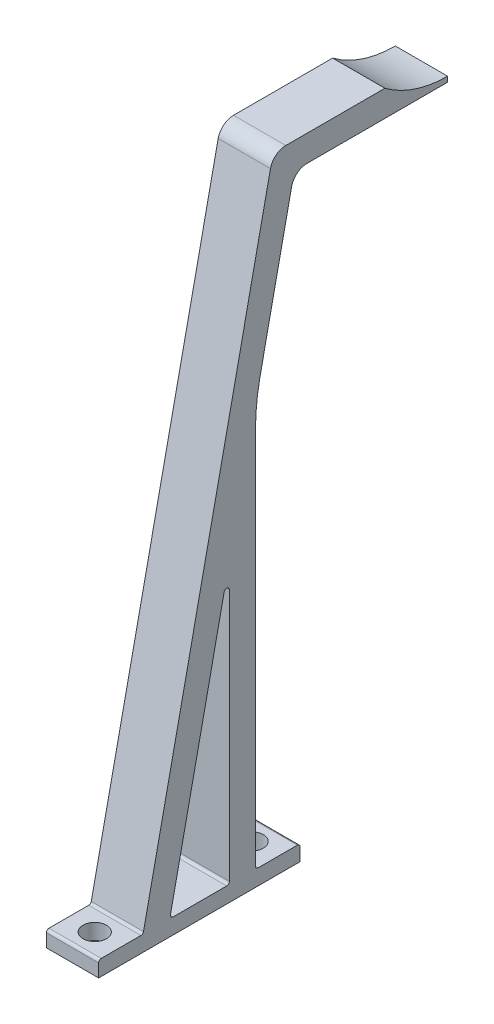
SolidWorks part; units mm, degrees
ref_plane "Front Plane" through (0, 0, 0) normal (0, 0, 1) x (1, 0, 0)
ref_plane "Top Plane" through (0, 0, 0) normal (0, 1, 0) x (1, 0, 0)
ref_plane "Right Plane" through (0, 0, 0) normal (1, 0, 0) x (0, 0, -1)
sketch "Sketch1" plane through (0, 0, 0) normal (1, 0, 0) x (0, 0, -1)
  line L0 (19.3948, 104.7187) -> (-4.885, -9.509)
  line L1 (-13.4692, -12.905) -> (25.0308, -12.905)
  line L2 (25.0308, -12.905) -> (25.0308, -10.405)
  line L3 (24.5308, -9.905) -> (17.0308, -9.905)
  line L4 (16.5308, -9.405) -> (16.5308, 62.9917)
  line L5 (53.2808, 103.095) -> (53.2808, 102.095)
  line L6 (22.3293, 107.095) -> (41.2808, 107.095)
  line L7 (53.2808, 102.095) -> (26.3782, 102.095)
  line L8 (-5.3741, -9.905) -> (-12.9692, -9.905)
  line L9 (-13.4692, -10.405) -> (-13.4692, -12.905)
  line L10 (17.4049, 71.3082) -> (23.4438, 99.7187)
  line L11 (0.76, -9.905) -> (11.0308, -9.905)
  line L12 (11.5308, -9.405) -> (11.5308, 38.9155)
  line L13 (10.5417, 39.0195) -> (0.2709, -9.3011)
  arc A0 (53.2808, 103.095) -> (41.2808, 107.095) centre (53.2808, 123.095) cw
  arc A1 (0.76, -9.905) -> (0.2709, -9.3011) centre (0.76, -9.405) cw
  arc A2 (16.5308, 62.9917) -> (17.4049, 71.3082) centre (56.5308, 62.9917) cw
  arc A3 (26.3782, 102.095) -> (23.4438, 99.7187) centre (26.3782, 99.095) ccw
  arc A4 (19.3948, 104.7187) -> (22.3293, 107.095) centre (22.3293, 104.095) cw
  arc A5 (-4.885, -9.509) -> (-5.3741, -9.905) centre (-5.3741, -9.405) cw
  arc A6 (17.0308, -9.905) -> (16.5308, -9.405) centre (17.0308, -9.405) cw
  arc A7 (-12.9692, -9.905) -> (-13.4692, -10.405) centre (-12.9692, -10.405) ccw
  arc A8 (25.0308, -10.405) -> (24.5308, -9.905) centre (24.5308, -10.405) ccw
  arc A9 (11.0308, -9.905) -> (11.5308, -9.405) centre (11.0308, -9.405) ccw
  arc A10 (11.5308, 38.9155) -> (10.5417, 39.0195) centre (11.0308, 38.9155) ccw
  point P26 (-4.9692, -9.905)
  point P29 (16.5308, -9.905)
  point P38 (0, 0)
  point P39 (0, 0)
  dimension "D1" = 20
  dimension "D12" = 40
  dimension "D13" = 3
  dimension "D14" = 3
  dimension "D16" = 0.5
  dimension "D17" = 0.5
  dimension "D18" = 0.5
  dimension "D19" = 0.5
  dimension "D22" = 0.5
  dimension "D23" = 0.5
  dimension "D24" = 0.5
  dimension "D2" = 120
  dimension "D3" = 8.5
  dimension "D4" = 3
  dimension "D5" = 5
  dimension "D6" = 66.75
  dimension "D7" = 1
  dimension "D8" = 38.5
  dimension "D9" = 8.5
  dimension "D10" = 5
  dimension "D11" = 66.75
  dimension "D15" = 102
  dimension "D20" = 5
  dimension "D21" = 5
extrude "Boss-Extrude1" add sketch "Sketch1" along normal blind 10 contours L0 A5 L8 A7 L9 L1 L2 A8 L3 A6 L4 A2 L10 A3 L7 L5 A0 L6 A4
extrude "Cut-Extrude2" cut sketch "Sketch1<5>" along normal blind 10 flip side to cut
sketch "Sketch1<5>" plane through (0, 0, 0) normal (1, 0, 0) x (0, 0, -1) same geometry as "Sketch1"
sketch "Sketch5" plane through (0, -12.905, 0) normal (0, -1, 0) x (1, 0, 0)
  line L2 (5, 13.4692) -> (5, -25.0308) construction
  line L3 (10, 13.4692) -> (0, 13.4692) construction
  line L4 (10, -25.0308) -> (0, -25.0308) construction
  circle A0 centre (5, 9.2192) radius 2.25
  circle A1 centre (5, -20.7808) radius 2.25
  point P4 (0, 0)
  point P5 (0, 0)
  point P6 (0, 0)
  dimension "D1" = 4.5
  dimension "D2" = 4.5
  dimension "D3" = 4.25
  dimension "D4" = 4.25
extrude "Cut-Extrude3" cut sketch "Sketch5" against normal blind 10
